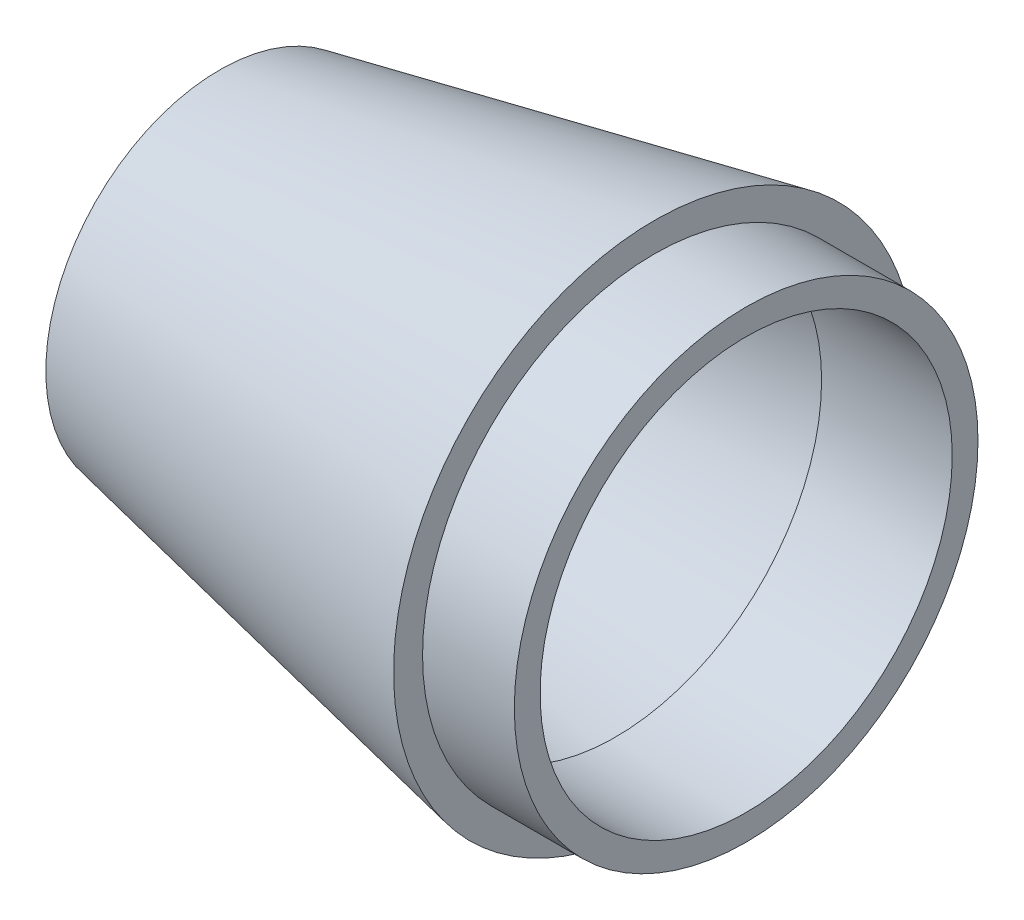
SolidWorks part; units mm, degrees
ref_plane "Front Plane" through (0, 0, 0) normal (0, 0, 1) x (1, 0, 0)
ref_plane "Top Plane" through (0, 0, 0) normal (0, 1, 0) x (1, 0, 0)
ref_plane "Right Plane" through (0, 0, 0) normal (1, 0, 0) x (0, 0, -1)
sketch "Sketch1" plane through (0, 0, 0) normal (0, 0, 1) x (1, 0, 0)
  line L0 (-12.065, 7.62) -> (-12.065, 6.35)
  line L1 (44.7264, 0) -> (-69.8413, 0) construction
  line L2 (6.985, 11.43) -> (6.985, 10.16)
  line L3 (-12.065, 0) -> (14.2126, 0) construction
  line L4 (-7.4776, 8.5375) -> (-7.4776, 0)
  line L5 (6.985, 11.43) -> (-12.065, 7.62)
  line L6 (-12.065, 6.35) -> (6.985, 10.16)
  line L7 (-7.4776, 0) -> (-2.54, 0)
  line L8 (-2.54, 0) -> (-2.54, 9.525)
  line L9 (-2.54, 9.525) -> (-7.4776, 8.5375)
  line L11 (10.9743, 9.0306) -> (5.2819, 9.0306)
  line L12 (5.2819, 9.0306) -> (5.2819, 9.8194)
  line L13 (5.2819, 9.8194) -> (6.985, 10.16)
  line L14 (6.985, 10.16) -> (11.0065, 10.16)
  line L15 (11.0065, 9.0306) -> (10.9743, 9.0306)
  line L16 (11.0065, 10.16) -> (11.0065, 9.0306)
  dimension "D1" = 19.05
  dimension "D2" = 1.27
  dimension "D3" = 7.62
  dimension "D4" = 11.43
  dimension "D5" = 1.27
revolve "Revolve4" add sketch "Sketch1" angle 360 about L1 region at (-9.7713, 7.4437, 0) region at (-4.9565, 3.8859, 0) region at (2.2225, 9.8425, 0)
sketch "Sketch2" plane through (-2.54, 0, 0) normal (1, 0, 0) x (0, 0, -1)
  line L3 (-0.3129, 0) -> (0.3129, 0)
  line L4 (-0.3129, 0) -> (-0.3129, 1.0082)
  line L5 (-0.3129, 1.0082) -> (0.3129, 1.0082)
  line L6 (0.3129, 0) -> (0.3129, 1.0082)
  line L9 (-0.3129, 1.0082) -> (0.3129, 1.0082)
  line L10 (-0.3129, 1.0082) -> (-0.3129, 0.7863)
  line L11 (-0.3129, 0.7863) -> (0.3129, 0.7863)
  line L12 (0.3129, 1.0082) -> (0.3129, 0.7863)
  point P3 (0, 0)
  point P8 (0, 0)
revolve "Revolve5" add sketch "Sketch2" angle 180 about L3 region at (-2.54, 0.8972, 0)
